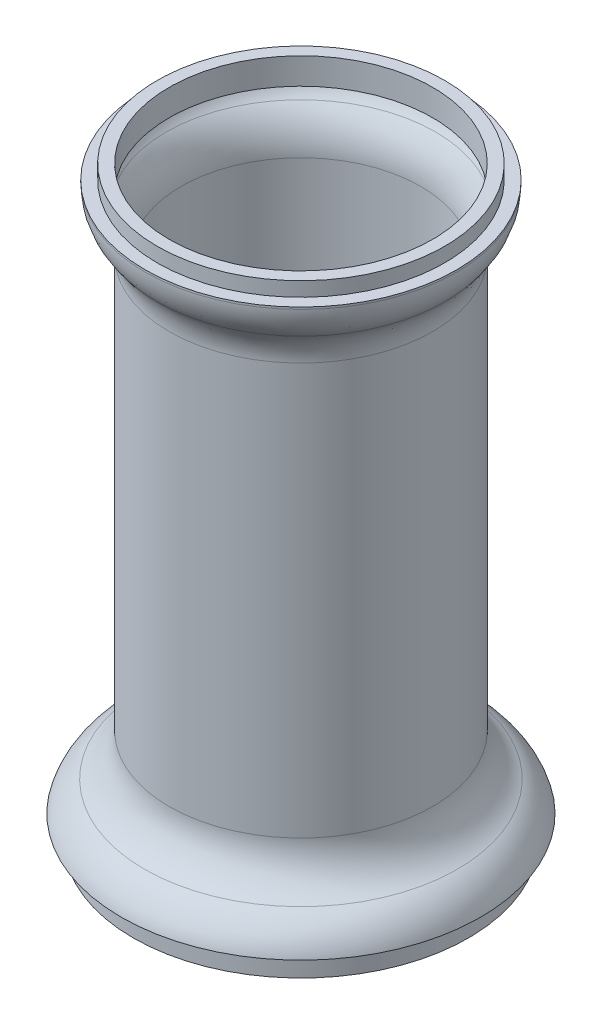
SolidWorks part; units mm, degrees
material "2024 Alloy"
ref_plane "Front Plane" through (0, 0, 0) normal (0, 0, 1) x (1, 0, 0)
ref_plane "Top Plane" through (0, 0, 0) normal (0, 1, 0) x (1, 0, 0)
ref_plane "Right Plane" through (0, 0, 0) normal (1, 0, 0) x (0, 0, -1)
sketch "Sketch1" plane through (0, 0, 0) normal (0, 1, 0) x (1, 0, 0)
  circle A0 centre (0, 0) radius 35
  dimension "D1" = 70
extrude "Boss-Extrude1" add sketch "Sketch1" along normal blind 5
sketch "Sketch3" plane through (0, 5, 0) normal (0, 1, 0) x (1, 0, 0)
  circle A0 centre (0, 0) radius 37.5
  dimension "D1" = 75
extrude "Boss-Extrude2" add sketch "Sketch3" along normal blind 5
sketch "Sketch4" plane through (0, 10, 0) normal (0, 1, 0) x (1, 0, 0)
  circle A0 centre (0, 0) radius 27.5
  dimension "D1" = 55
extrude "Boss-Extrude5" add sketch "Sketch4" along normal blind 104.5 contours A0
sketch "Sketch5" plane through (0, 114.5, 0) normal (0, 1, 0) x (1, 0, 0)
  circle A0 centre (0, 0) radius 32.5
  dimension "D1" = 65
extrude "Boss-Extrude6" add sketch "Sketch5" along normal blind 5 contours A0
sketch "Sketch6" plane through (0, 119.5, 0) normal (0, 1, 0) x (1, 0, 0)
  circle A0 centre (0, 0) radius 30
  dimension "D1" = 60
extrude "Boss-Extrude7" add sketch "Sketch6" along normal blind 3
fillet "Fillet1" radius 10 2 edges at (0, 10, 27.5) (0, 114.5, 27.5)
fillet "Fillet2" radius 10 2 edges at (0, 114.5, 32.5) (0, 10, 37.5)
shell "Shell1" thickness 2.5 removed face at (0, 0, 35) removed face at (0, 122.5, 30)
